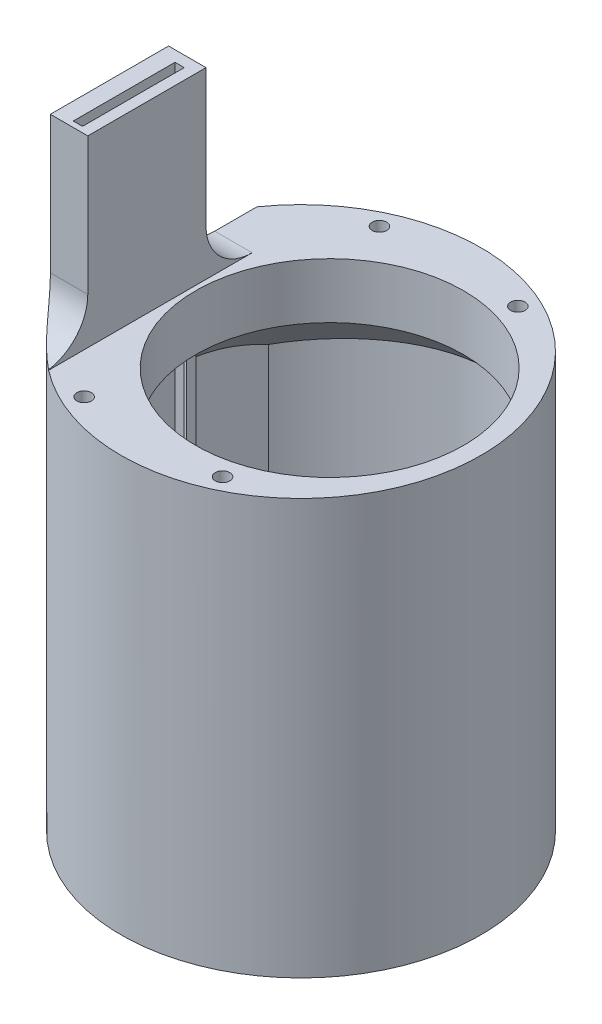
SolidWorks part; units mm, degrees
ref_plane "Front Plane" through (0, 0, 0) normal (0, 0, 1) x (1, 0, 0)
ref_plane "Top Plane" through (0, 0, 0) normal (0, 1, 0) x (1, 0, 0)
ref_plane "Right Plane" through (0, 0, 0) normal (1, 0, 0) x (0, 0, -1)
sketch "Sketch1" plane through (0, 0, 0) normal (0, 1, 0) x (1, 0, 0)
  line L4 (-21.8318, 28.9478) -> (-21.8318, -28.9478) construction
  line L12 (-40.5643, -28.4211) -> (-40.5643, 28.4211)
  arc A0 (-40.5643, -28.4211) -> (-40.5643, 28.4211) centre (0, 0) ccw
  circle A2 centre (-21.8318, 17.8353) radius 7.9375 construction
  circle A3 centre (-21.8318, 17.8353) radius 11.1125 construction
  circle A4 centre (-21.8318, 17.8353) radius 15.875 construction
  point P3 (-21.8318, 0)
  dimension "D1" = 99.06
  dimension "D2" = 40.5643
  dimension "D6" = 15.875
  dimension "7/8" = 22.225
  dimension "D7" = 18.7325
  dimension "D3" = 4.7625
  dimension "D4" = 57.8955
extrude "Boss-Extrude1" add sketch "Sketch1" along normal mid plane 114.3
sketch "Sketch2" plane through (0, -57.15, 0) normal (0, -1, 0) x (1, 0, 0)
  circle A0 centre (-21.8318, -17.8353) radius 7.9375
  dimension "D1" = 15.875
shell "Shell3" thickness 4.7625 removed face at (4.4829, 57.15, 0)
extrude "Cut-Extrude3" cut sketch "Sketch2" against normal blind 7.62 contours A0
sketch "Sketch6" plane through (0, 57.15, 0) normal (0, 1, 0) x (1, 0, 0)
  line L0 (-29.0035, 0) -> (44.7675, 0) construction
  arc A0 (-35.8018, -26.8768) -> (-35.8018, 26.8768) centre (0, 0) ccw construction
  circle A1 centre (7.882, 0) radius 36.8855
  point P7 (7.882, 0)
  point P11 (44.7675, 0)
  dimension "D1" = 73.771
sketch "Sketch9" plane through (0, 0, 0) normal (0, 0, 1) x (1, 0, 0)
  line L0 (-29.0035, 57.15) -> (-29.0035, 41.91)
  line L1 (-29.0035, 41.91) -> (-54.4035, 16.51)
  line L2 (-54.4035, 16.51) -> (-54.4035, 57.15)
  line L3 (-54.4035, 57.15) -> (-29.0035, 57.15)
  dimension "D1" = 15.24
  dimension "D2" = 25.4
  dimension "D3" = 45
ref_axis "Axis1" through (7.882, 57.15, 0) along (0, 1, 0)
revolve "Revolve1" add sketch "Sketch9" angle 360 about axis through (7.882, 57.15, 0) along (0, 1, 0)
sketch "Sketch10" plane through (0, -57.15, 0) normal (0, -1, 0) x (1, 0, 0)
  line L0 (-40.5643, 28.4211) -> (-40.5643, -28.4211) construction
  line L1 (-40.5643, 28.4211) -> (-40.5643, -28.4211)
  arc A0 (-40.5643, -28.4211) -> (-40.5643, 28.4211) centre (0, 0) ccw construction
  arc A1 (-40.5643, -28.4211) -> (-40.5643, 28.4211) centre (0, 0) ccw
  circle A2 centre (7.882, 0) radius 62.2855
  circle A3 centre (7.882, 0) radius 62.2855 construction
extrude "Cut-Extrude4" cut sketch "Sketch10" against normal through all
sketch "Sketch11" plane through (0, 57.15, 0) normal (0, 1, 0) x (1, 0, 0)
  line L1 (-35.8018, -26.8768) -> (-33.2618, -26.8768)
  line L2 (-35.8018, -26.8768) -> (-35.8018, 1.1232)
  line L3 (-35.8018, 1.1232) -> (-33.2618, 1.1232)
  line L4 (-33.2618, -26.8768) -> (-33.2618, 1.1232)
  dimension "D1" = 2.54
  dimension "D2" = 28
extrude "Cut-Extrude5" cut sketch "Sketch11" against normal up to next
sketch "Sketch12" plane through (0, 57.15, 0) normal (0, 1, 0) x (1, 0, 0)
  line L0 (-33.2618, -26.8768) -> (-33.2618, 1.1232) construction
  line L1 (-40.5643, -28.4211) -> (-30.2618, -28.4211)
  line L2 (-40.5643, -28.4211) -> (-40.5643, 4.1232)
  line L3 (-40.5643, 4.1232) -> (-30.2618, 4.1232)
  line L4 (-30.2618, -28.4211) -> (-30.2618, 4.1232)
  line L5 (-33.2618, 1.1232) -> (-35.8018, 1.1232) construction
  line L7 (-35.8018, -26.8768) -> (-33.2618, -26.8768)
  line L8 (-35.8018, -26.8768) -> (-35.8018, 1.1232)
  line L9 (-35.8018, 1.1232) -> (-33.2618, 1.1232)
  line L10 (-33.2618, -26.8768) -> (-33.2618, 1.1232)
  point P9 (-34.5318, 1.1232)
  line M5 (-33.2618, -26.8768) -> (-35.8018, -26.8768)
  line M6 (-35.8018, -26.8768) -> (-35.8018, 1.1232)
  line M7 (-35.8018, 1.1232) -> (-33.2618, 1.1232)
  line M8 (-33.2618, 1.1232) -> (-33.2618, -26.8768)
  line M10 (-40.5643, 28.4211) -> (-40.5643, -28.4211)
  dimension "D1" = 3
  dimension "D2" = 3
extrude "Boss-Extrude3" add sketch "Sketch12" along normal offset from surface (50.4825 mm away) 160.02 contours L1 L4 L3 M10 M8 M5 M6 M7 region at (-40.2229, 57.15, 12.149) up to face at (-21.8318, -52.3875, -9.8978) offset beyond the face yes
fillet "Fillet1" radius 12.7 2 edges at (-35.413, 57.15, -4.1232) (-35.413, 57.15, 28.4211)
sketch "Sketch15" plane through (0, 57.15, 0) normal (0, 1, 0) x (1, 0, 0)
  line L1 (-19.05, 40.64) -> (19.05, 40.64)
  line L2 (-19.05, 40.64) -> (-19.05, -40.64)
  line L3 (-19.05, -40.64) -> (19.05, -40.64)
  line L4 (19.05, 40.64) -> (19.05, -40.64)
  line L5 (-19.05, 40.64) -> (19.05, -40.64) construction
  line L6 (-19.05, -40.64) -> (19.05, 40.64) construction
  point P0 (0, 0)
  dimension "D1" = 81.28
  dimension "D2" = 38.1
hole_wizard "CBORE for M3 SBHCS1" positions "Sketch16" profile "Sketch17" counterbore size "M3" standard "ANSI Metric"
sketch "Sketch16" plane through (0, 57.15, 0) normal (0, 1, 0) x (1, 0, 0)
  point P0 (-19.05, 40.64)
  point P3 (19.05, 40.64)
  point P6 (19.05, -40.64)
  point P9 (-19.05, -40.64)
sketch "Sketch17" plane through (-19.05, 57.15, -40.64) normal (1, 0, 0) x (0, 0, 1)
  line L0 (0, 0) -> (0, 11.1815)
  line L1 (0, 11.1815) -> (1.7, 10.16)
  line L2 (1.7, 10.16) -> (1.7, 6)
  line L3 (1.7, 6) -> (2, 6)
  line L4 (2, 6) -> (2, 0)
  line L5 (2, 0) -> (0, 0)
  line L10 (0, 11.1815) -> (-1.7, 10.16) construction
  line L11 (0, -6.35) -> (0, 107.95) construction
  dimension "Hole Dia." = 3.4
  dimension "Hole Depth" = 10.16
  dimension "C'Bore Dia." = 4
  dimension "C'Bore Depth" = 6
  dimension "Drill Angle" = 118
sketch "Sketch18" plane through (0, -52.3875, 0) normal (0, 1, 0) x (1, 0, 0)
  line L0 (-35.8018, -26.8768) -> (-33.2618, -26.8768)
  line L1 (-33.2618, -26.8768) -> (-29.3266, -23.5748)
  line L2 (-29.3266, -23.5748) -> (-29.3266, -26.1148)
  line L3 (-29.3266, -26.1148) -> (-33.5405, -29.6507)
  line L4 (-35.8018, 26.8768) -> (-35.8018, -26.8768) construction
  line L5 (-35.8018, 3.6632) -> (-33.2618, 3.6632)
  line L6 (-35.8018, 3.6632) -> (-35.8018, 1.1232)
  line L7 (-35.8018, 1.1232) -> (-33.2618, 1.1232)
  line L8 (-33.2618, 3.6632) -> (-33.2618, 1.1232) construction
  line L9 (-33.2618, 1.1232) -> (-29.3266, -2.1788)
  line L10 (-29.3266, -2.1788) -> (-29.3266, 0.3612)
  line L11 (-29.3266, 0.3612) -> (-33.2618, 3.6632)
  arc A0 (-35.8018, -26.8768) -> (-35.8018, 26.8768) centre (0, 0) ccw construction
  arc A1 (-33.5405, -29.6507) -> (-35.8018, -26.8768) centre (0, 0) cw
  dimension "D1" = 2.54
  dimension "D2" = 3.302
  dimension "D3" = 140
  dimension "D4" = 2.54
  dimension "D5" = 28
extrude "Boss-Extrude5" add sketch "Sketch18" along normal up to next
sketch "Sketch19" plane through (0, -57.15, 0) normal (0, -1, 0) x (1, 0, 0)
  arc A0 (-24.3926, 39) -> (27.3313, 37) centre (0, 0) cw
  arc A1 (-24.3926, -39) -> (27.3313, -37) centre (0, 0) ccw
  dimension "D1" = 46
  dimension "D2" = 78
  dimension "D3" = 74
sketch "Sketch20" plane through (0, -57.15, 0) normal (0, -1, 0) x (-1, 0, 0)
  circle A0 centre (-27.3313, 37) radius 3.53
  circle A1 centre (24.3926, 39) radius 3.53
  circle A2 centre (-27.3313, -37) radius 3.53
  circle A3 centre (24.3926, -39) radius 3.53
  arc A6 (40.5643, 28.4211) -> (40.5643, -28.4211) centre (0, 0) ccw construction
extrude "Boss-Extrude6" add sketch "Sketch20" against normal blind 10
fillet "Fillet2" radius 3 4 edges at (25.2339, -52.3875, 34.1607) (25.2339, -52.3875, -34.1607) (-22.5208, -52.3875, -36.0072) (-22.5208, -52.3875, 36.0072)
fillet "Fillet3" radius 2 4 edges at (25.2339, -47.15, 34.1607) (-22.5208, -47.15, 36.0072) (25.2339, -47.15, -34.1607) (-22.5208, -47.15, -36.0072)
hole_wizard "CBORE for M3 SHCS1" positions "Sketch21" profile "Sketch22" counterbore size "M3" standard "ANSI Metric"
sketch "Sketch21" plane through (0, -57.15, 0) normal (0, -1, 0) x (-1, 0, 0)
  point P0 (24.3926, -39)
  point P3 (-27.3313, -37)
  point P6 (-27.3313, 37)
  point P9 (24.3926, 39)
sketch "Sketch22" plane through (-24.3926, -57.15, 39) normal (1, 0, 0) x (0, 0, -1)
  line L0 (0, 0) -> (0, 8.0215)
  line L1 (0, 8.0215) -> (1.7, 7)
  line L2 (1.7, 7) -> (1.7, 6)
  line L3 (1.7, 6) -> (2, 6)
  line L4 (2, 6) -> (2, 0)
  line L5 (2, 0) -> (0, 0)
  line L10 (0, 8.0215) -> (-1.7, 7) construction
  line L11 (0, -6.35) -> (0, 107.95) construction
  dimension "Hole Dia." = 3.4
  dimension "Hole Depth" = 7
  dimension "C'Bore Dia." = 4
  dimension "C'Bore Depth" = 6
  dimension "Drill Angle" = 118
equation "\"D1@Sketch6\"=(2.865in)+1mm"
